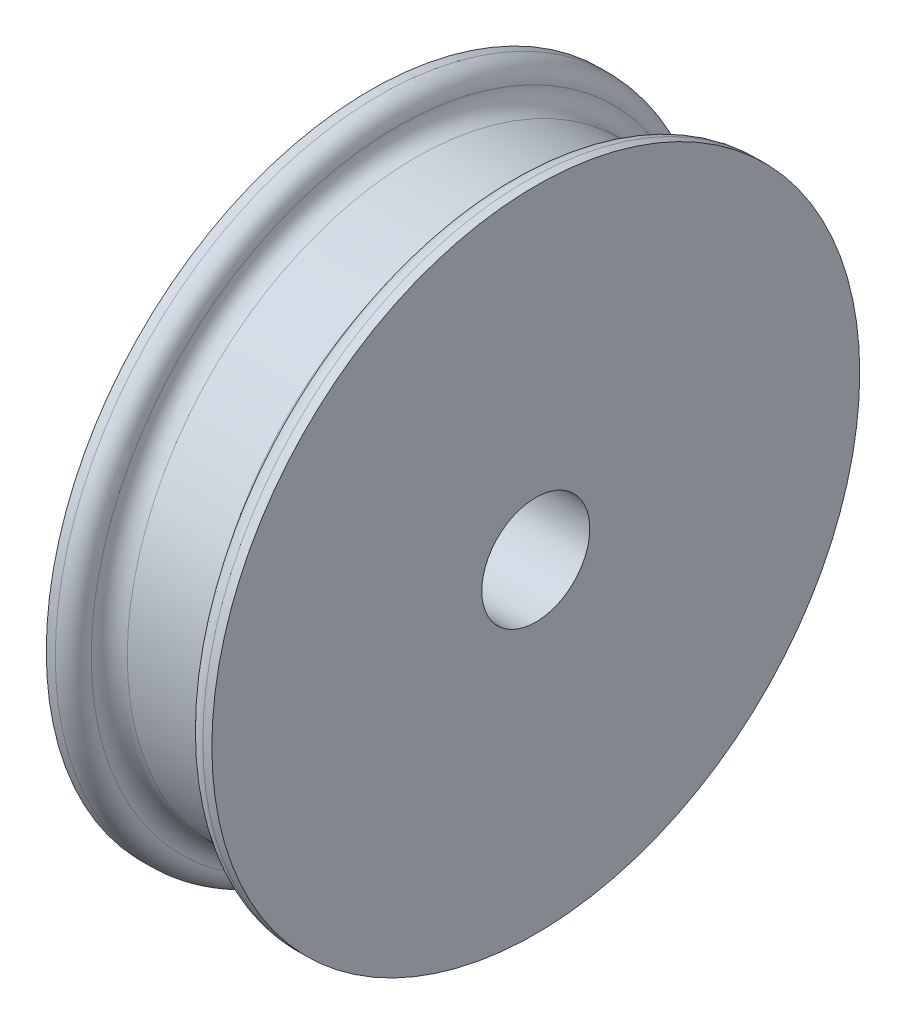
SolidWorks part; units mm, degrees
ref_plane "Front" through (0, 0, 0) normal (0, 0, 1) x (1, 0, 0)
ref_plane "Top" through (0, 0, 0) normal (0, 1, 0) x (1, 0, 0)
ref_plane "Right" through (0, 0, 0) normal (1, 0, 0) x (0, 0, -1)
sketch "Sketch1" plane through (0, 0, 0) normal (0, 0, 1) x (1, 0, 0)
  line L0 (-2.3, 1.5) -> (2.3, 1.5)
  line L1 (2.3, 1.5) -> (2.3, 9)
  line L2 (2.3, 9) -> (1.55, 9)
  line L3 (1.55, 9) -> (1.55, 8.5)
  line L4 (1.05, 8) -> (-1.05, 8)
  line L5 (0, 8) -> (0, 1.5) construction
  line L6 (0, 0) -> (4.984, 0) construction
  line L7 (-1.55, 9) -> (-1.55, 8.5)
  line L8 (-2.3, 9) -> (-1.55, 9)
  line L9 (-2.3, 1.5) -> (-2.3, 9)
  arc A0 (1.55, 8.5) -> (1.05, 8) centre (1.05, 8.5) cw
  arc A1 (-1.55, 8.5) -> (-1.05, 8) centre (-1.05, 8.5) ccw
  point P9 (0, 8)
  point P16 (1.55, 8)
  point P19 (-1.55, 8)
  dimension "D6" = 0.5
  dimension "D1" = 3
  dimension "D2" = 16
  dimension "D3" = 1
  dimension "D4" = 2.3
  dimension "D5" = 0.75
revolve "Revolve1" add sketch "Sketch1" angle 360 about L6
ref_point "Point1"
fillet "Fillet1" radius 0.5 2 edges at (-1.55, 0, 9) (1.55, 0, 9)
